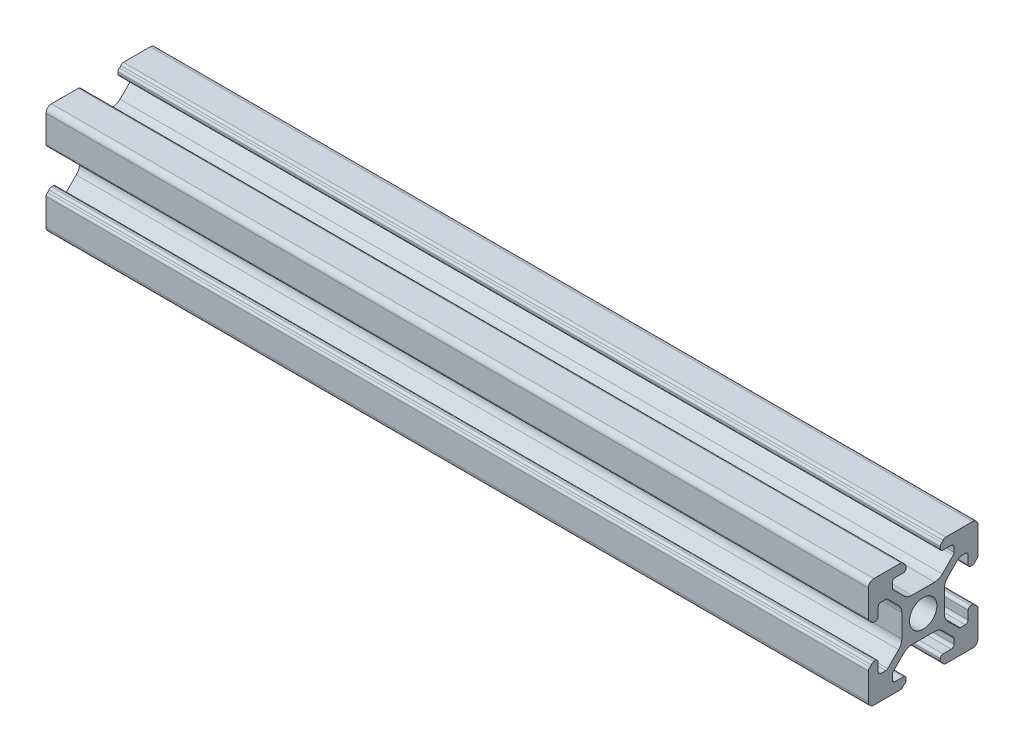
SolidWorks part; units mm, degrees
material "6063-O, Extruded Rod (SS)"
ref_plane "Front Plane" through (0, 0, 0) normal (0, 0, 1) x (1, 0, 0)
ref_plane "Top Plane" through (0, 0, 0) normal (0, 1, 0) x (1, 0, 0)
ref_plane "Right Plane" through (0, 0, 0) normal (1, 0, 0) x (0, 0, -1)
sketch "Sketch1" plane through (0, 0, 0) normal (1, 0, 0) x (0, 0, -1)
  line L0 (10, 10) -> (-10, -10) construction
  line L1 (-10, 10) -> (10, 10)
  line L2 (-10, 10) -> (-10, -10)
  line L3 (-10, -10) -> (10, -10)
  line L4 (10, 10) -> (10, -10)
  dimension "D1" = 20
extrude "Boss-Extrude1" add sketch "Sketch1" along normal blind 150
fillet "Fillet1" radius 1 4 edges at (75, -10, -10) (75, -10, 10) (75, 10, -10) (75, 10, 10)
sketch "Sketch3" plane through (0, 0, 0) normal (-1, 0, 0) x (0, 0, 1)
  line L0 (-3.6, 10) -> (3.6, 10)
  line L1 (-9, 10) -> (9, 10) construction
  line L2 (3.6, 10) -> (3.6, 9.5)
  line L3 (3.6, 9.5) -> (3.1, 9.5)
  line L4 (3.1, 9.5) -> (3.1, 8.2)
  line L5 (3.1, 8.2) -> (5.63, 8.2)
  line L6 (5.63, 8.2) -> (5.63, 6.6199)
  line L7 (5.63, 6.6199) -> (2.9101, 3.9)
  line L8 (2.9101, 3.9) -> (-2.9101, 3.9)
  line L9 (-2.9101, 3.9) -> (-5.63, 6.6199)
  line L10 (-5.63, 6.6199) -> (-5.63, 8.2)
  line L11 (-5.63, 8.2) -> (-3.1, 8.2)
  line L12 (-3.1, 8.2) -> (-3.1, 9.5)
  line L13 (-3.1, 9.5) -> (-3.6, 9.5)
  line L14 (-3.6, 9.5) -> (-3.6, 10)
  line L15 (0, 10) -> (0, 3.9) construction
  line L16 (10, 3.6) -> (10, -3.6)
  line L17 (10, -3.6) -> (9.5, -3.6)
  line L18 (9.5, -3.6) -> (9.5, -3.1)
  line L19 (9.5, -3.1) -> (8.2, -3.1)
  line L20 (8.2, -3.1) -> (8.2, -5.63)
  line L21 (8.2, -5.63) -> (6.6199, -5.63)
  line L22 (6.6199, -5.63) -> (3.9, -2.9101)
  line L23 (3.9, -2.9101) -> (3.9, 2.9101)
  line L24 (3.9, 2.9101) -> (6.6199, 5.63)
  line L25 (6.6199, 5.63) -> (8.2, 5.63)
  line L26 (8.2, 5.63) -> (8.2, 3.1)
  line L27 (8.2, 3.1) -> (9.5, 3.1)
  line L28 (9.5, 3.1) -> (9.5, 3.6)
  line L29 (9.5, 3.6) -> (10, 3.6)
  line L30 (10, 0) -> (3.9, 0) construction
  line L31 (3.6, -10) -> (-3.6, -10)
  line L32 (-3.6, -10) -> (-3.6, -9.5)
  line L33 (-3.6, -9.5) -> (-3.1, -9.5)
  line L34 (-3.1, -9.5) -> (-3.1, -8.2)
  line L35 (-3.1, -8.2) -> (-5.63, -8.2)
  line L36 (-5.63, -8.2) -> (-5.63, -6.6199)
  line L37 (-5.63, -6.6199) -> (-2.9101, -3.9)
  line L38 (-2.9101, -3.9) -> (2.9101, -3.9)
  line L39 (2.9101, -3.9) -> (5.63, -6.6199)
  line L40 (5.63, -6.6199) -> (5.63, -8.2)
  line L41 (5.63, -8.2) -> (3.1, -8.2)
  line L42 (3.1, -8.2) -> (3.1, -9.5)
  line L43 (3.1, -9.5) -> (3.6, -9.5)
  line L44 (3.6, -9.5) -> (3.6, -10)
  line L45 (0, -10) -> (0, -3.9) construction
  line L46 (-10, -3.6) -> (-10, 3.6)
  line L47 (-10, 3.6) -> (-9.5, 3.6)
  line L48 (-9.5, 3.6) -> (-9.5, 3.1)
  line L49 (-9.5, 3.1) -> (-8.2, 3.1)
  line L50 (-8.2, 3.1) -> (-8.2, 5.63)
  line L51 (-8.2, 5.63) -> (-6.6199, 5.63)
  line L52 (-6.6199, 5.63) -> (-3.9, 2.9101)
  line L53 (-3.9, 2.9101) -> (-3.9, -2.9101)
  line L54 (-3.9, -2.9101) -> (-6.6199, -5.63)
  line L55 (-6.6199, -5.63) -> (-8.2, -5.63)
  line L56 (-8.2, -5.63) -> (-8.2, -3.1)
  line L57 (-8.2, -3.1) -> (-9.5, -3.1)
  line L58 (-9.5, -3.1) -> (-9.5, -3.6)
  line L59 (-9.5, -3.6) -> (-10, -3.6)
  line L60 (-10, 0) -> (-3.9, 0) construction
  line L61 (10, 9) -> (10, -9) construction
  line L62 (-10, -9) -> (-10, 9) construction
  point P4 (0, 10)
  point P17 (0, 0)
  point P26 (10, 0)
  point P43 (0, -10)
  point P60 (-10, 0)
  point P75 (0, 0)
  dimension "D1" = 135
  dimension "D2" = 6.2
  dimension "D3" = 7.2
  dimension "D4" = 6.1
  dimension "D5" = 11.26
  dimension "D6" = 0.5
  dimension "D8" = 1.4
  dimension "D9" = 1.8
  dimension "D7" = 4
extrude "Cut-Extrude1" cut sketch "Sketch3" against normal through all
hole_wizard "Ø5.0 (5) Diameter Hole1" positions "Sketch4" profile "Sketch5" hole size "Ø5.0" standard "ANSI Metric" end condition through all
sketch "Sketch4" plane through (0, 0, 0) normal (-1, 0, 0) x (0, 0, 1)
  point P0 (0, 0)
sketch "Sketch5" plane through (0, 0, 0) normal (0, 1, 0) x (0, 0, 1)
  line L0 (0, 0) -> (0, 150)
  line L1 (0, 150) -> (2.5, 150)
  line L2 (2.5, 150) -> (2.5, 0)
  line L5 (2.5, 0) -> (0, 0)
  line L11 (0, -6.35) -> (0, 107.95) construction
  dimension "Thru Hole Dia." = 5
  dimension "Thru Hole Depth" = 150
fillet "Fillet2" radius 2 8 edges at (75, -3.9, -2.9101) (75, -3.9, 2.9101) (75, -2.9101, 3.9) (75, 2.9101, 3.9) (75, 3.9, 2.9101) (75, 3.9, -2.9101) (75, 2.9101, -3.9) (75, -2.9101, -3.9)
fillet "Fillet3" radius 0.5 20 edges at (75, 3.6, -10) (75, 3.1, -9.5) (75, 3.1, -8.2) (75, 5.63, -8.2) (75, 5.63, -6.6199) (75, 3.6, 10) (75, 3.1, 9.5) (75, 3.1, 8.2) (75, 5.63, 8.2) (75, 5.63, 6.6199) (75, 6.6199, 5.63) (75, 8.2, 5.63) (75, 8.2, 3.1) (75, 9.5, 3.1) (75, 10, 3.6) (75, 9.5, -3.1) (75, 10, -3.6) (75, 8.2, -3.1) (75, 8.2, -5.63) (75, 6.6199, -5.63)
fillet "Fillet4" radius 0.5 20 edges at (75, -3.6, 10) (75, -3.1, 9.5) (75, -3.1, 8.2) (75, -5.63, 8.2) (75, -5.63, 6.6199) (75, -6.6199, 5.63) (75, -8.2, 5.63) (75, -8.2, 3.1) (75, -10, 3.6) (75, -9.5, 3.1) (75, -10, -3.6) (75, -9.5, -3.1) (75, -8.2, -3.1) (75, -8.2, -5.63) (75, -6.6199, -5.63) (75, -5.63, -6.6199) (75, -5.63, -8.2) (75, -3.1, -8.2) (75, -3.1, -9.5) (75, -3.6, -10)
fillet "Fillet5" radius 0.5 8 edges at (75, 3.6, -9.5) (75, -3.6, -9.5) (75, -9.5, -3.6) (75, -9.5, 3.6) (75, -3.6, 9.5) (75, 3.6, 9.5) (75, 9.5, 3.6) (75, 9.5, -3.6)
